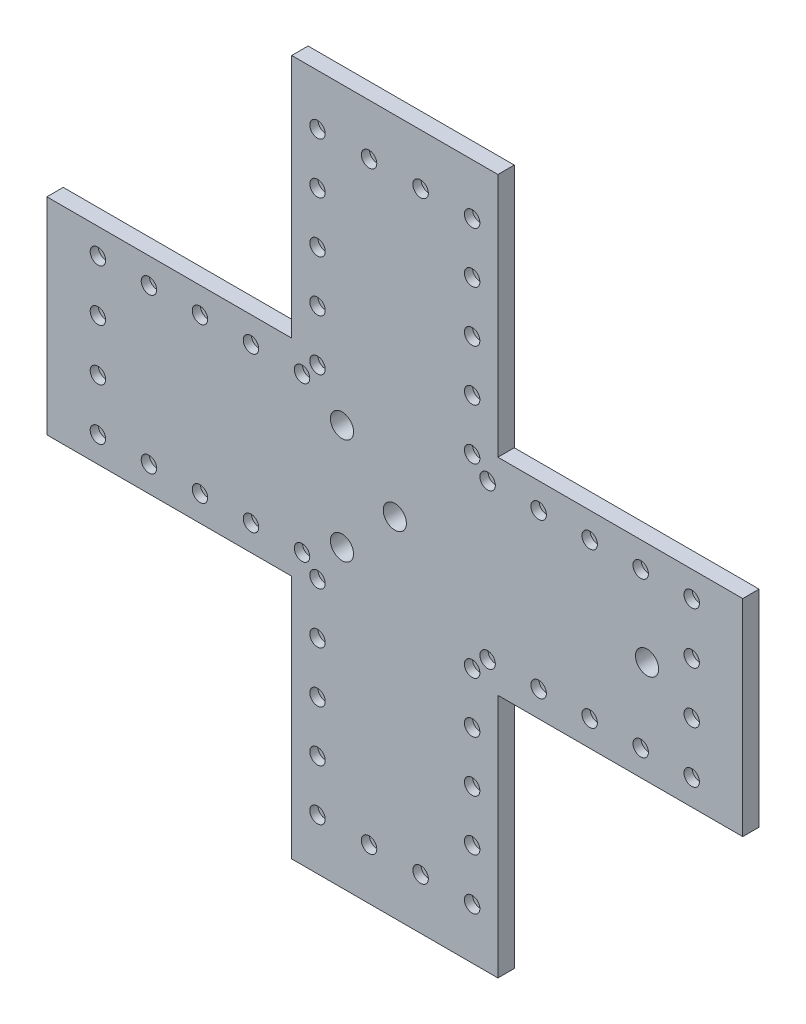
SolidWorks part; units mm, degrees
ref_plane "Front Plane" through (0, 0, 0) normal (0, 0, 1) x (1, 0, 0)
ref_plane "Top Plane" through (0, 0, 0) normal (0, 1, 0) x (1, 0, 0)
ref_plane "Right Plane" through (0, 0, 0) normal (1, 0, 0) x (0, 0, -1)
sketch "Sketch1" plane through (0, 0, 0) normal (0, 0, 1) x (1, 0, 0)
  line L0 (0, 67.5) -> (0, -67.5) construction
  line L1 (20, 67.5) -> (-20, 67.5)
  line L2 (20, 67.5) -> (20, -67.5)
  line L3 (20, -67.5) -> (-20, -67.5)
  line L4 (-20, 67.5) -> (-20, -67.5)
  line L5 (-67.5, 20) -> (67.5, 20)
  line L6 (-67.5, 20) -> (-67.5, -20)
  line L7 (-67.5, -20) -> (67.5, -20)
  line L8 (67.5, 20) -> (67.5, -20)
  line L9 (-67.5, 0) -> (67.5, 0) construction
  line L10 (57.6, 15) -> (47.7, 15) construction
  line L11 (47.7, 15) -> (37.8, 15) construction
  line L12 (37.8, 15) -> (27.9, 15) construction
  line L13 (18, 15) -> (27.9, 15) construction
  line L14 (-15, 57.6) -> (-15, 47.7) construction
  line L15 (-15, 47.7) -> (-15, 37.8) construction
  line L16 (-15, 37.8) -> (-15, 27.9) construction
  line L17 (-15, 27.9) -> (-15, 18) construction
  circle A0 centre (-10.253, 10.253) radius 2.2479
  circle A1 centre (0, 0) radius 2.2479
  circle A2 centre (48.94, 0) radius 2.2479
  circle A3 centre (-10.253, -10.253) radius 2.2479
  circle A6 centre (27.9, 15) radius 1.5
  circle A7 centre (37.8, 15) radius 1.5
  circle A8 centre (47.7, 15) radius 1.5
  circle A9 centre (57.6, 15) radius 1.5
  circle A10 centre (18, 15) radius 1.5
  circle A12 centre (57.6, 5) radius 1.5
  circle A14 centre (27.9, -15) radius 1.5
  circle A15 centre (37.8, -15) radius 1.5
  circle A16 centre (47.7, -15) radius 1.5
  circle A17 centre (57.6, -5) radius 1.5
  circle A18 centre (57.6, -15) radius 1.5
  circle A19 centre (18, -15) radius 1.5
  circle A20 centre (-18, -15) radius 1.5
  circle A21 centre (-27.9, -15) radius 1.5
  circle A22 centre (-37.8, -15) radius 1.5
  circle A23 centre (-47.7, -15) radius 1.5
  circle A24 centre (-57.6, -15) radius 1.5
  circle A25 centre (-57.6, -5) radius 1.5
  circle A26 centre (-57.6, 5) radius 1.5
  circle A27 centre (-37.8, 15) radius 1.5
  circle A28 centre (-47.7, 15) radius 1.5
  circle A29 centre (-57.6, 15) radius 1.5
  circle A30 centre (-27.9, 15) radius 1.5
  circle A31 centre (-18, 15) radius 1.5
  circle A32 centre (-15, 57.6) radius 1.5
  circle A33 centre (-5, 57.6) radius 1.5
  circle A34 centre (-15, 47.7) radius 1.5
  circle A35 centre (-15, 37.8) radius 1.5
  circle A36 centre (-15, 27.9) radius 1.5
  circle A37 centre (-15, 18) radius 1.5
  circle A39 centre (15, 18) radius 1.5
  circle A40 centre (15, 27.9) radius 1.5
  circle A41 centre (15, 37.8) radius 1.5
  circle A42 centre (15, 47.7) radius 1.5
  circle A43 centre (15, 57.6) radius 1.5
  circle A44 centre (5, 57.6) radius 1.5
  circle A45 centre (-15, -18) radius 1.5
  circle A46 centre (-15, -27.9) radius 1.5
  circle A47 centre (-15, -37.8) radius 1.5
  circle A48 centre (-15, -47.7) radius 1.5
  circle A49 centre (-15, -57.6) radius 1.5
  circle A50 centre (-5, -57.6) radius 1.5
  circle A51 centre (5, -57.6) radius 1.5
  circle A52 centre (15, -57.6) radius 1.5
  circle A53 centre (15, -47.7) radius 1.5
  circle A54 centre (15, -37.8) radius 1.5
  circle A55 centre (15, -27.9) radius 1.5
  circle A56 centre (15, -18) radius 1.5
  circle A57 centre (-10.253, 10.253) radius 1.725
  circle A58 centre (0, 0) radius 1.725
  circle A59 centre (-10.253, -10.253) radius 1.725
  circle A60 centre (48.94, 0) radius 1.725
  point P12 (0, 0)
  point P23 (67.5, 0)
  point P24 (0, 67.5)
  point P26 (-20, 0)
  point P28 (0, -20)
  dimension "D7" = 3
  dimension "D11" = 3
  dimension "D14" = 3.45
  dimension "D1" = 40
  dimension "D2" = 135
  dimension "D3" = 135
  dimension "D4" = 9.9
  dimension "D5" = 9.9
  dimension "D6" = 5
  dimension "D8" = 47.5
  dimension "D9" = 10
  dimension "D10" = 10
  dimension "D12" = 9.9
  dimension "D13" = 5
extrude "Boss-Extrude1" add sketch "Sketch1" along normal blind 3.175 contours L4 L7 L2 L5 A56 A39 A37 A19 A10 A3 A1 A0 A20 A31 A45 | L4 L5 L2 L1 A43 A41 A32 A33 A34 A35 A36 A40 A42 A44 | L8 L5 L2 L7 A17 A15 A2 A6 A7 A8 A9 A12 A14 A16 A18 | L6 L7 L4 L5 A29 A27 A21 A22 A23 A24 A25 A26 A28 A30 | L7 L4 L3 L2 A55 A54 A53 A52 A51 A49 A47 A46 A48 A50 region at (0, 43.6739, 0) region at (43.6278, 0, 0) region at (19.4343, 0, 0) region at (-43.6739, 0, 0) region at (0, -43.6739, 0)
extrude "Boss-Extrude2" add sketch "Sketch1<6>" along normal blind 1.5875 contours A10 | A39 | A6 | A7 | A8 | A12 | A17 | A18 | A16 | A15 | A19 | A56 | A14 | A55 | A53 | A54 | A52 | A51 | A50 | A49 | A48 | A47 | A46 | A45 | A20 | A21 | A22 | A23 | A24 | A25 | A29 | A26 | A28 | A27 | A37 | A31 | A30 | A36 | A34 | A35 | A32 | A33 | A44 | A43 | A42 | A41 | A40 | A9 region at (27.9, 15, 0) region at (37.8, 15, 0) region at (47.7, 15, 0) region at (57.6, 15, 0) region at (18, 15, 0) region at (57.6, 5, 0) region at (27.9, -15, 0) region at (37.8, -15, 0) region at (47.7, -15, 0) region at (57.6, -5, 0) region at (57.6, -15, 0) region at (18, -15, 0) region at (-18, -15, 0) region at (-27.9, -15, 0) region at (-37.8, -15, 0) region at (-47.7, -15, 0) region at (-57.6, -15, 0) region at (-57.6, -5, 0) region at (-57.6, 5, 0) region at (-37.8, 15, 0) region at (-47.7, 15, 0) region at (-57.6, 15, 0) region at (-27.9, 15, 0) region at (-18, 15, 0) region at (-15, 57.6, 0) region at (-5, 57.6, 0) region at (-15, 47.7, 0) region at (-15, 37.8, 0) region at (-15, 27.9, 0) region at (-15, 18, 0) region at (15, 18, 0) region at (15, 27.9, 0) region at (15, 37.8, 0) region at (15, 47.7, 0) region at (15, 57.6, 0) region at (5, 57.6, 0) region at (-15, -18, 0) region at (-15, -27.9, 0) region at (-15, -37.8, 0) region at (-15, -47.7, 0) region at (-15, -57.6, 0) region at (-5, -57.6, 0) region at (5, -57.6, 0) region at (15, -57.6, 0) region at (15, -47.7, 0) region at (15, -37.8, 0) region at (15, -27.9, 0) region at (15, -18, 0)
sketch "Sketch1<6>" plane through (0, 0, 0) normal (0, 0, 1) x (1, 0, 0) same geometry as "Sketch1"
equation "\"D11@Sketch1\"=\"D7@Sketch1\""
